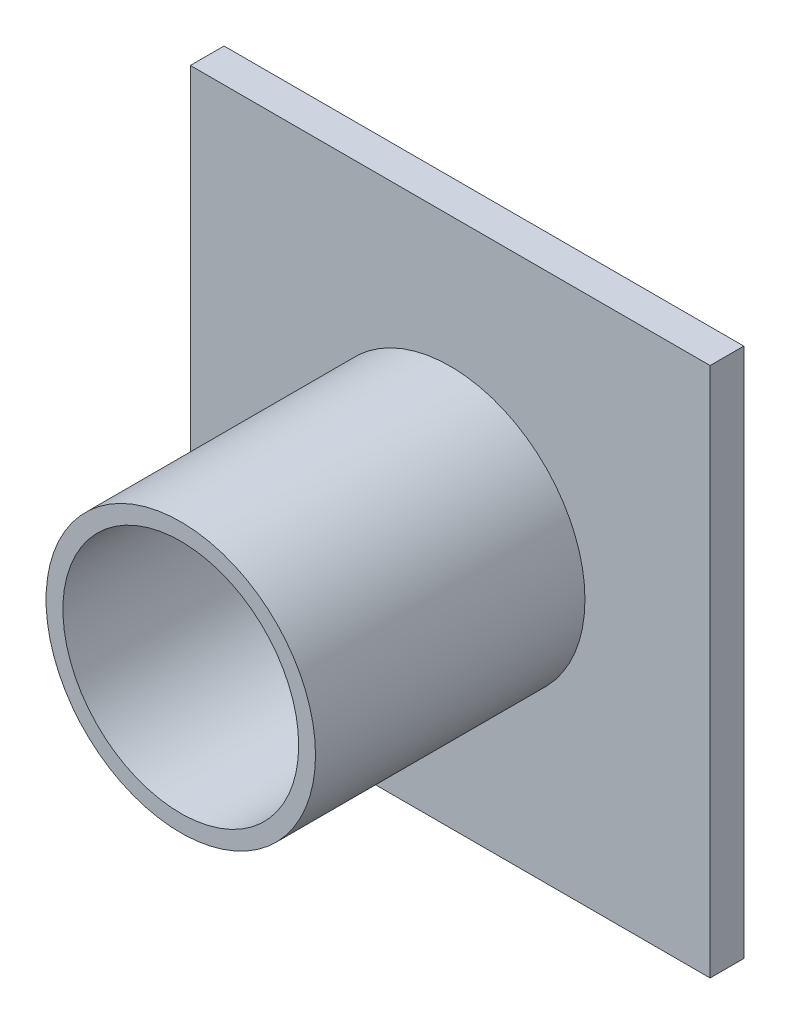
SolidWorks part; units mm, degrees
ref_plane "Front Plane" through (0, 0, 0) normal (0, 0, 1) x (1, 0, 0)
ref_plane "Top Plane" through (0, 0, 0) normal (0, 1, 0) x (1, 0, 0)
ref_plane "Right Plane" through (0, 0, 0) normal (1, 0, 0) x (0, 0, -1)
sketch "Sketch1" plane through (0, 0, 0) normal (0, 0, 1) x (1, 0, 0)
  line L1 (-17.8804, 0) -> (80.1096, 0)
  line L2 (-17.8804, 0) -> (-17.8804, -100)
  line L3 (-17.8804, -100) -> (80.1096, -100)
  line L4 (80.1096, 0) -> (80.1096, -100)
extrude "Boss-Extrude1" add sketch "Sketch1" along normal blind 6.35
sketch "Sketch2" plane through (0, 0, 6.35) normal (0, 0, 1) x (1, 0, 0)
  circle A0 centre (31.1146, -50) radius 25.4
  circle A1 centre (31.1146, -50) radius 22.225
extrude "Boss-Extrude2" add sketch "Sketch2" along normal blind 50.8
ref_axis "CenterAxis" through (31.1146, -50, 57.15) along (0, 0, -1)
